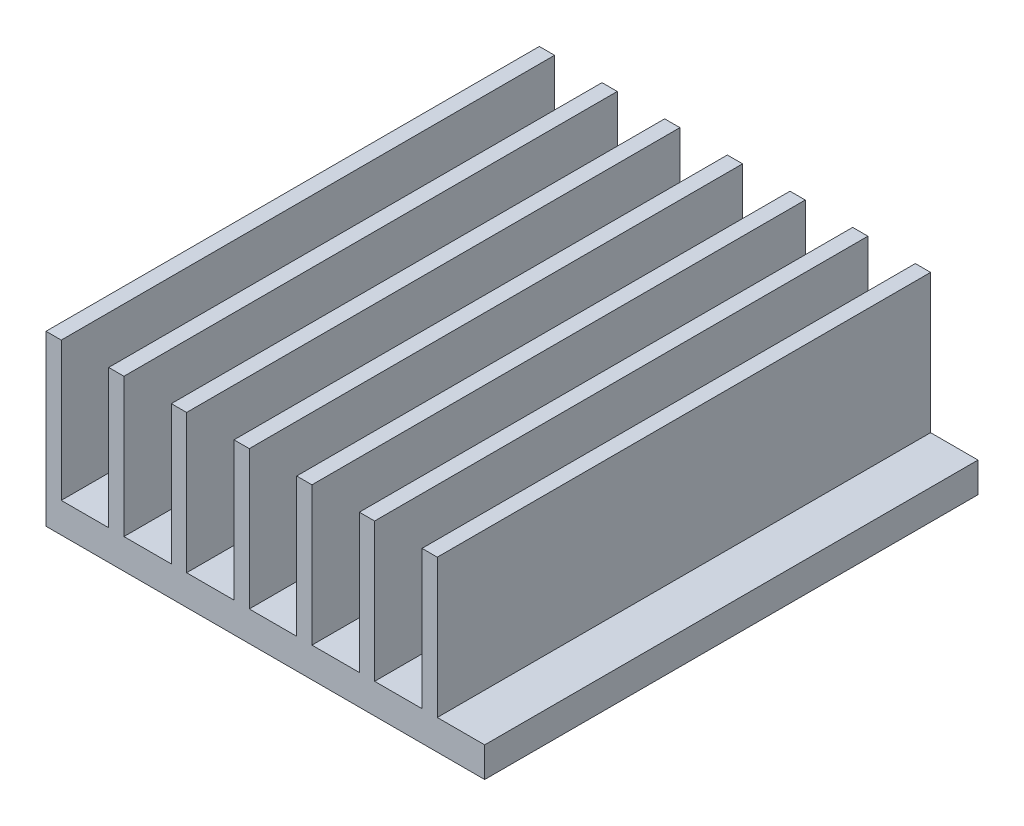
SolidWorks part; units mm, degrees
ref_plane "Front Plane" through (0, 0, 0) normal (0, 0, 1) x (1, 0, 0)
ref_plane "Top Plane" through (0, 0, 0) normal (0, 1, 0) x (1, 0, 0)
ref_plane "Right Plane" through (0, 0, 0) normal (1, 0, 0) x (0, 0, -1)
sketch "Sketch1" plane through (0, 0, 0) normal (0, 0, 1) x (1, 0, 0)
  line L0 (0, 26.6954) -> (0, 4.7498)
  line L1 (0, 26.6954) -> (2.413, 26.6954)
  line L2 (2.413, 26.6954) -> (2.413, 4.7498)
  line L3 (2.413, 4.7498) -> (9.906, 4.7498)
  line L4 (9.906, 4.7498) -> (9.906, 26.6954)
  line L5 (0, 4.7498) -> (75.1086, 4.7498) construction
  line L6 (0, 26.6954) -> (75.1086, 26.6954) construction
  line L7 (0, 4.7498) -> (0, 0)
  line L8 (9.906, 26.6954) -> (12.319, 26.6954)
  line L9 (12.319, 26.6954) -> (12.319, 4.7498)
  line L10 (12.319, 4.7498) -> (19.812, 4.7498)
  line L11 (19.812, 4.7498) -> (19.812, 26.6954)
  line L12 (19.812, 26.6954) -> (22.225, 26.6954)
  line L13 (22.225, 26.6954) -> (22.225, 4.7498)
  line L14 (22.225, 4.7498) -> (29.718, 4.7498)
  line L15 (29.718, 4.7498) -> (29.718, 26.6954)
  line L16 (29.718, 26.6954) -> (32.131, 26.6954)
  line L17 (32.131, 26.6954) -> (32.131, 4.7498)
  line L18 (32.131, 4.7498) -> (39.624, 4.7498)
  line L19 (39.624, 4.7498) -> (39.624, 26.6954)
  line L20 (39.624, 26.6954) -> (42.037, 26.6954)
  line L21 (42.037, 26.6954) -> (42.037, 4.7498)
  line L22 (42.037, 4.7498) -> (49.53, 4.7498)
  line L23 (49.53, 4.7498) -> (49.53, 26.6954)
  line L24 (49.53, 26.6954) -> (51.943, 26.6954)
  line L25 (51.943, 26.6954) -> (51.943, 4.7498)
  line L26 (51.943, 4.7498) -> (59.436, 4.7498)
  line L27 (59.436, 4.7498) -> (59.436, 26.6954)
  line L28 (59.436, 26.6954) -> (61.849, 26.6954)
  line L29 (61.849, 26.6954) -> (61.849, 4.7498)
  line L30 (61.849, 4.7498) -> (61.849, 0) construction
  line L31 (61.849, 0) -> (0, 0)
  line L32 (0, 26.6954) -> (9.906, 26.6954) construction
  line L33 (61.849, 0) -> (69.342, 0)
  line L34 (69.342, 0) -> (69.342, 4.7498)
  line L35 (69.342, 4.7498) -> (61.849, 4.7498)
  line L53 (61.849, 4.7498) -> (69.342, 4.7498) [skipped]
  line L54 (69.342, 4.7498) -> (69.342, 26.6954) [skipped]
  dimension "D1" = 4.7498
  dimension "D2" = 26.6954
  dimension "D3" = 2.413
  dimension "D4" = 7.493
  dimension "D5" = 9.906
  dimension "D7" = 7.493
  dimension "D6" = 7
extrude "Boss-Extrude1" add sketch "Sketch1" along normal up to surface (77.978 mm away) contours L31 L30 L29 L28 L27 L26 L25 L24 L23 L22 L21 L20 L19 L18 L17 L16 L15 L14 L13 L12 L11 L10 L9 L8 L4 L3 L2 L1 L0 L7 region at (1.2065, 25.9524, 0)
ref_plane "Plane1" through (6.1595, 0, 0) normal (1, 0, 0) x (0, 0, -1)
equation "\"D5@Sketch1\"=\"D4@Sketch1\"+\"D3@Sketch1\""
equation "\"D7@Sketch1\"=\"D4@Sketch1\""
